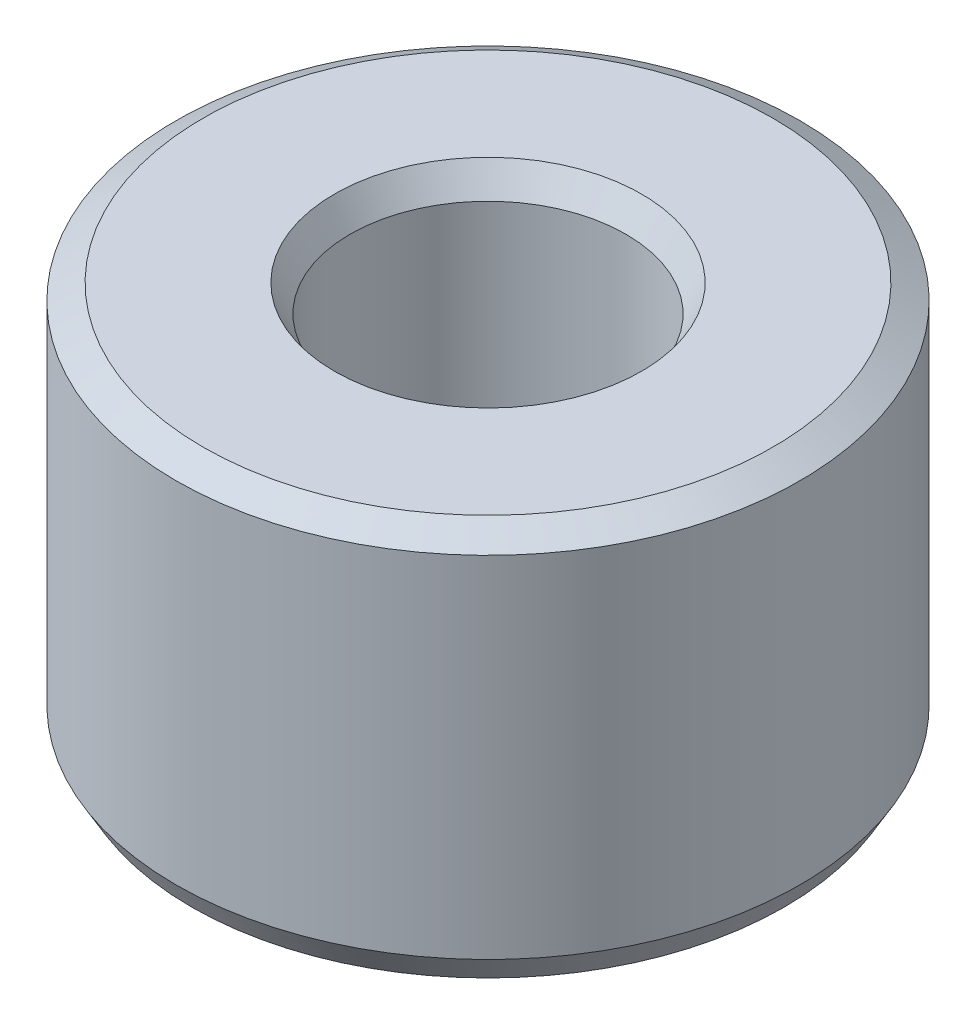
SolidWorks part; units mm, degrees
ref_plane "Front Plane" through (0, 0, 0) normal (0, 0, 1) x (1, 0, 0)
ref_plane "Top Plane" through (0, 0, 0) normal (0, 1, 0) x (1, 0, 0)
ref_plane "Right Plane" through (0, 0, 0) normal (1, 0, 0) x (0, 0, -1)
sketch "Sketch1" plane through (0, 0, 0) normal (0, 1, 0) x (1, 0, 0)
  circle A0 centre (0, 0) radius 57.5
  dimension "SLEEVE_OD" = 115
extrude "Boss-Extrude1" add sketch "Sketch1" along normal blind 72.3743
sketch "Sketch2" plane through (0, 0, 0) normal (0, 1, 0) x (1, 0, 0)
  circle A0 centre (0, 0) radius 25.4305
  dimension "BORE_D" = 50.8611
extrude "Cut-Extrude1" cut sketch "Sketch2" along normal through all
chamfer "Chamfer1" distance 2.8758 angle 60 4 edges at (0, 72.3743, 25.4305) (0, 0, 25.4305) (0, 0, 57.5) (0, 72.3743, 57.5) first distance on face at (0, 72.3743, 25.4305) first distance on face at (0, 0, 25.4305) first distance on face at (0, 72.3743, 57.5)
